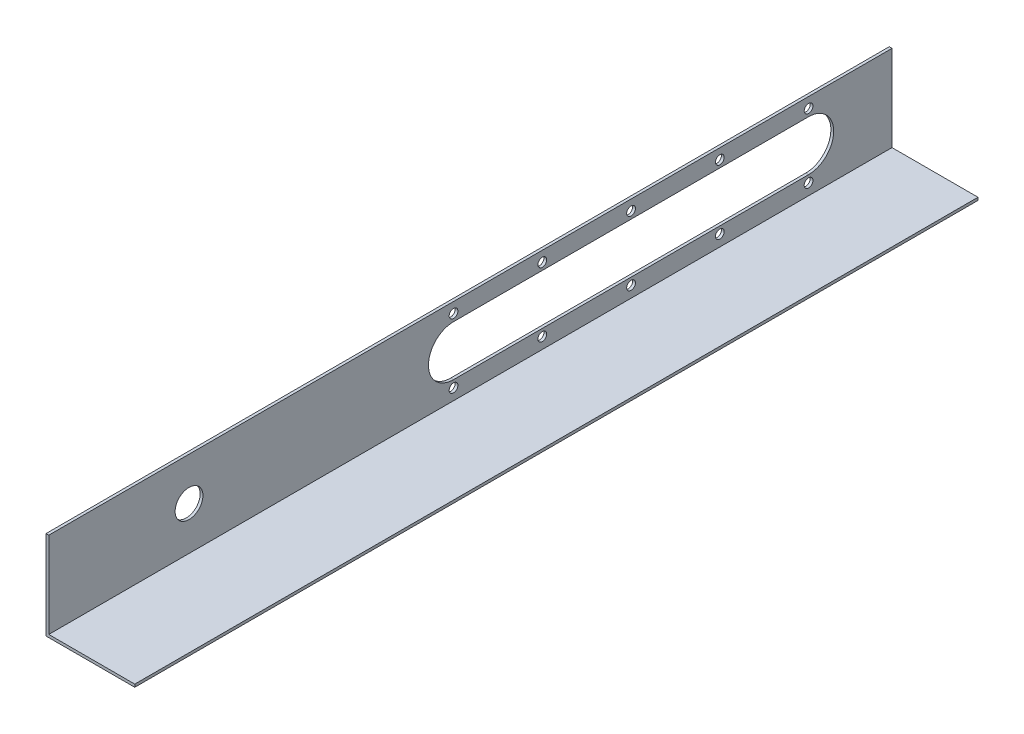
SolidWorks part; units mm, degrees
material "6061 Alloy"
ref_plane "Front Plane" through (0, 0, 0) normal (0, 0, 1) x (1, 0, 0)
ref_plane "Top Plane" through (0, 0, 0) normal (0, 1, 0) x (1, 0, 0)
ref_plane "Right Plane" through (0, 0, 0) normal (1, 0, 0) x (0, 0, -1)
sketch "Sketch3" plane through (0, 0, 0) normal (0, 0, 1) x (1, 0, 0)
  line L0 (0, 0) -> (0, 49.2125)
  line L1 (0, 49.2125) -> (-1.5875, 49.2125)
  line L2 (-1.5875, 49.2125) -> (-1.5875, -1.5875)
  line L3 (-1.5875, -1.5875) -> (49.2125, -1.5875)
  line L4 (49.2125, -1.5875) -> (49.2125, 0)
  line L5 (49.2125, 0) -> (0, 0)
  dimension "D1" = 1.5875
  dimension "D2" = 1.5875
  dimension "D3" = 50.8
  dimension "D4" = 50.8
extrude "Boss-Extrude2" add sketch "Sketch3" along normal blind 431.8
sketch "Sketch6" plane through (0, 0, 0) normal (1, 0, 0) x (0, 0, -1)
  line L0 (-250.952, 24.8285) -> (-47.752, 24.8285) construction
  line L1 (-250.952, 39.1795) -> (-47.752, 39.1795)
  line L2 (-250.952, 10.4775) -> (-47.752, 10.4775)
  line L4 (0, 0) -> (0, 49.2125) construction
  line L5 (-431.8, 49.2125) -> (0, 49.2125) construction
  arc A0 (-250.952, 39.1795) -> (-250.952, 10.4775) centre (-250.952, 24.8285) ccw
  arc A1 (-47.752, 10.4775) -> (-47.752, 39.1795) centre (-47.752, 24.8285) ccw
  point P2 (-149.352, 24.8285)
  dimension "D3" = 47.752
  dimension "D1" = 28.702
  dimension "D2" = 203.2
  dimension "D4" = 24.384
extrude "Cut-Extrude3" cut sketch "Sketch6" against normal blind 127
sketch "Sketch7" plane through (0, 0, 0) normal (1, 0, 0) x (0, 0, -1)
  line L1 (-431.8, 49.2125) -> (0, 49.2125) construction
  line L2 (0, 0) -> (0, 49.2125) construction
  circle A0 centre (-402.336, 24.7736) radius 7.9629
  dimension "D1" = 15.9258
  dimension "D3" = 24.4389
  dimension "D4" = 402.336
extrude "Cut-Extrude4" cut sketch "Sketch7" against normal through all
sketch "Sketch8" plane through (0, 0, 0) normal (1, 0, 0) x (0, 0, -1)
  line L2 (-47.752, 43.2435) -> (-250.952, 43.2435)
  line L3 (-47.752, 43.2435) -> (-250.952, 43.2435) construction
  line L4 (-250.952, 43.2435) -> (-149.352, 43.2435) construction
  line L5 (-250.952, 6.4135) -> (-47.752, 6.4135)
  line L6 (-250.952, 6.4135) -> (-47.752, 6.4135) construction
  line L7 (-149.352, 43.2435) -> (-47.752, 43.2435) construction
  line L8 (-250.952, 6.4135) -> (-149.352, 6.4135) construction
  line L9 (-149.352, 6.4135) -> (-47.752, 6.4135) construction
  point P0 (-149.352, 6.4135)
  point P1 (-250.952, 43.2435)
  point P6 (-250.952, 6.4135)
  point P7 (-149.352, 43.2435)
  point P8 (-200.152, 43.2435)
  point P9 (-47.752, 43.2435)
  point P10 (-47.752, 6.4135)
  point P13 (-98.552, 43.2435)
  point P14 (-200.152, 6.4135)
  point P15 (-98.552, 6.4135)
  dimension "D1" = 4.064
  dimension "D2" = 4.064
hole_wizard "#10 (0.1935) Diameter Hole1" positions "Sketch9" profile "Sketch10" hole size "#10" standard "ANSI Inch" end condition through all
sketch "Sketch9" plane through (0, 0, 0) normal (1, 0, 0) x (0, 0, -1)
  point P0 (-250.952, 43.2435)
  point P3 (-200.152, 43.2435)
  point P6 (-149.352, 43.2435)
  point P9 (-98.552, 43.2435)
  point P12 (-47.752, 43.2435)
  point P15 (-47.752, 6.4135)
  point P18 (-98.552, 6.4135)
  point P21 (-149.352, 6.4135)
  point P24 (-200.152, 6.4135)
  point P27 (-250.952, 6.4135)
sketch "Sketch10" plane through (0, 43.2435, 250.952) normal (0, 1, 0) x (0, 0, -1)
  line L0 (0, 0) -> (0, 1.5875)
  line L1 (0, 1.5875) -> (2.5, 1.5875)
  line L2 (2.5, 1.5875) -> (2.5, 0)
  line L5 (2.5, 0) -> (0, 0)
  line L11 (0, -6.35) -> (0, 107.95) construction
  dimension "Thru Hole Dia." = 5
  dimension "Thru Hole Depth" = 1.5875
sketch "Sketch13" plane through (0, 0, 431.8) normal (0, 0, 1) x (1, 0, 0)
  point P0 (-1.5875, -1.5875)
  line M1 (49.2125, 0) -> (0, 0)
  line M2 (0, 0) -> (0, 49.2125)
  line M3 (0, 49.2125) -> (-1.5875, 49.2125)
  line M4 (-1.5875, 49.2125) -> (-1.5875, -1.5875)
  line M5 (-1.5875, -1.5875) -> (49.2125, -1.5875)
  line M6 (49.2125, -1.5875) -> (49.2125, 0)
extrude "Boss-Extrude3" add sketch "Sketch13" along normal blind 50.8 contours M6 M1 M2 M3 M4 M5 region at (48.4941, -0.7937, 431.8)
sketch "Sketch14" plane through (0, -1.5875, 0) normal (0, -1, 0) x (1, 0, 0)
  line L0 (23.8125, 12.7) -> (23.8125, 222.25) construction
  line L1 (21.2328, 12.7) -> (21.2328, 222.25)
  line L2 (26.3922, 12.7) -> (26.3922, 222.25)
  line L3 (23.8125, 257.7703) -> (23.8125, 467.3203) construction
  line L4 (21.2328, 257.7703) -> (21.2328, 467.3203)
  line L5 (26.3922, 257.7703) -> (26.3922, 467.3203)
  line L6 (-1.5875, 0) -> (49.2125, 0) construction
  line L7 (-1.5875, 482.6) -> (49.2125, 482.6) construction
  arc A0 (21.2328, 12.7) -> (26.3922, 12.7) centre (23.8125, 12.7) ccw
  arc A1 (26.3922, 222.25) -> (21.2328, 222.25) centre (23.8125, 222.25) ccw
  arc A2 (21.2328, 257.7703) -> (26.3922, 257.7703) centre (23.8125, 257.7703) ccw
  arc A3 (26.3922, 467.3203) -> (21.2328, 467.3203) centre (23.8125, 467.3203) ccw
  point P2 (23.8125, 117.475)
  point P8 (23.8125, 362.5453)
  point P16 (23.8125, 469.9)
  dimension "D1" = 12.7
  dimension "D2" = 12.7
  dimension "D4" = 209.55
  dimension "D5" = 5.1594
